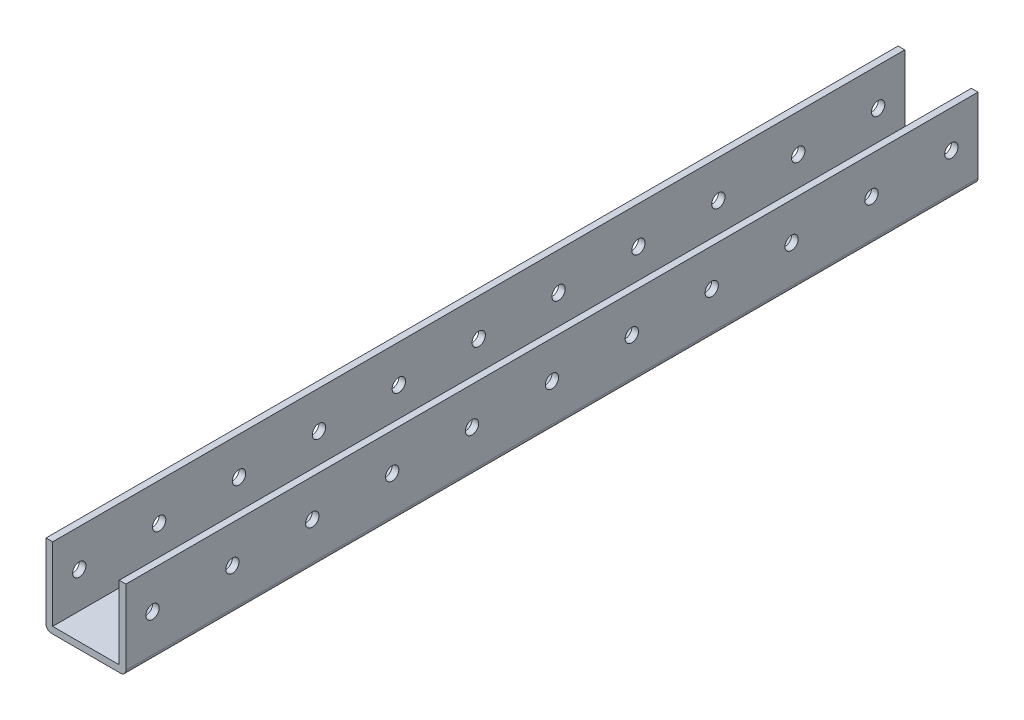
SolidWorks part; units mm, degrees
ref_plane "Front Plane" through (0, 0, 0) normal (0, 0, 1) x (1, 0, 0)
ref_plane "Top Plane" through (0, 0, 0) normal (0, 1, 0) x (1, 0, 0)
ref_plane "Right Plane" through (0, 0, 0) normal (1, 0, 0) x (0, 0, -1)
sketch "Sketch2" plane through (0, 0, 0) normal (0, 1, 0) x (1, 0, 0)
  line L1 (-19.05, -203.2) -> (19.05, -203.2)
  line L2 (-19.05, -203.2) -> (-19.05, 203.2)
  line L3 (-19.05, 203.2) -> (19.05, 203.2)
  line L4 (19.05, -203.2) -> (19.05, 203.2)
  line L5 (-19.05, -203.2) -> (19.05, 203.2) construction
  line L6 (-19.05, 203.2) -> (19.05, -203.2) construction
  point P0 (0, 0)
  dimension "D1" = 38.1
  dimension "D2" = 406.4
extrude "Boss-Extrude1" add sketch "Sketch2" along normal blind 38.1
sketch "Sketch3" plane through (0, 0, 203.2) normal (0, 0, 1) x (1, 0, 0)
  line L0 (-19.05, 38.1) -> (19.05, 38.1) construction
  line L1 (-15.875, 38.1) -> (15.875, 38.1)
  line L2 (-15.875, 38.1) -> (-15.875, 3.175)
  line L3 (-15.875, 3.175) -> (15.875, 3.175)
  line L4 (15.875, 38.1) -> (15.875, 3.175)
  line L5 (-19.05, 38.1) -> (-19.05, 0) construction
  line L6 (19.05, 38.1) -> (19.05, 0) construction
  line L7 (-19.05, 0) -> (19.05, 0) construction
  dimension "D1" = 3.175
  dimension "D2" = 3.175
  dimension "D3" = 3.175
extrude "Cut-Extrude1" cut sketch "Sketch3" against normal blind 406.4
fillet "Fillet1" radius 2.54 2 edges at (-19.05, 0, 0) (19.05, 0, 0)
sketch "Sketch4" plane through (19.05, 0, 0) normal (1, 0, 0) x (0, 0, -1)
  line L1 (-203.2, 38.1) -> (-203.2, 2.54) construction
  line L2 (203.2, 38.1) -> (203.2, 2.54) construction
  line L5 (-203.2, 2.54) -> (203.2, 2.54) construction
  circle A0 centre (-190.5, 20.32) radius 3.175
  circle A1 centre (-152.4, 20.32) radius 3.175
  circle A2 centre (-114.3, 20.32) radius 3.175
  circle A3 centre (-76.2, 20.32) radius 3.175
  circle A4 centre (-38.1, 20.32) radius 3.175
  circle A5 centre (0, 20.32) radius 3.175
  circle A6 centre (38.1, 20.32) radius 3.175
  circle A7 centre (76.2, 20.32) radius 3.175
  circle A8 centre (114.3, 20.32) radius 3.175
  circle A9 centre (152.4, 20.32) radius 3.175
  circle A10 centre (190.5, 20.32) radius 3.175
  dimension "D1" = 6.35
  dimension "D2" = 17.78
  dimension "D3" = 12.7
  dimension "D5" = 12.7
  dimension "D4" = 11
extrude "Cut-Extrude2" cut sketch "Sketch4" against normal blind 50.8
